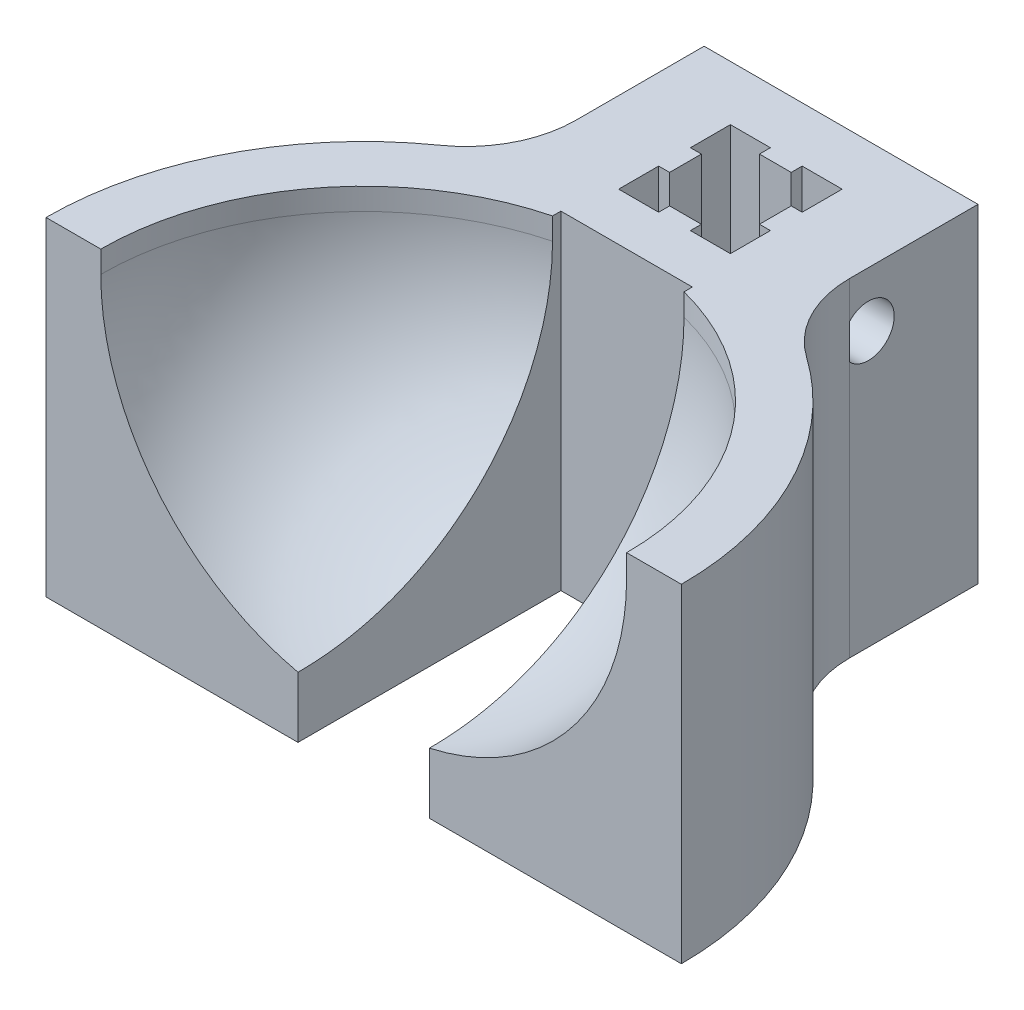
SolidWorks part; units mm, degrees
ref_plane "Front Plane" through (0, 0, 0) normal (0, 0, 1) x (1, 0, 0)
ref_plane "Top Plane" through (0, 0, 0) normal (0, 1, 0) x (1, 0, 0)
ref_plane "Right Plane" through (0, 0, 0) normal (1, 0, 0) x (0, 0, -1)
ref_axis "Axe1" through (0, -1.5691, 0) along (0, 1, 0)
sketch "Esquisse2" plane through (0, 0, 0) normal (-1, 0, 0) x (0, 0, 1)
  line L0 (-24, 30) -> (-29, 30)
  line L1 (-29, 30) -> (-29, 0)
  line L2 (-29, 0) -> (0, 0)
  line L3 (-1, 5) -> (0, 5)
  line L4 (-24, 30) -> (-24, 28)
  line L6 (0, 5) -> (0, 0)
  line L7 (0, -1.5691) -> (0, 32.9511) construction
  arc A0 (-24, 28) -> (-1, 5) centre (-1, 28) ccw
  dimension "D3" = 23
  dimension "D1" = 5
  dimension "D2" = 1
  dimension "D4" = 30
  dimension "D5" = 5
revolve "Révolution1" add sketch "Esquisse2" angle 180 mid plane about axis through (0, -1.5691, 0) along (0, 1, 0)
sketch "Esquisse3" plane through (0, 30, 0) normal (0, -1, 0) x (1, 0, 0)
  line L1 (-6, 0) -> (6, 0)
  line L2 (-6, 0) -> (-6, -24)
  line L3 (-6, -24) -> (6, -24)
  line L4 (6, 0) -> (6, -24)
  line L8 (-6, -28.3725) -> (6, -28.3725)
  line L9 (-6, -28.3725) -> (-6, -29)
  line L10 (-6, -29) -> (6, -29)
  line L11 (6, -28.3725) -> (6, -29)
  arc A0 (-29, 0) -> (29, 0) centre (0, 0) ccw construction
  arc A1 (-24, 0) -> (24, 0) centre (0, 0) ccw construction
  point P6 (0, 0)
  dimension "D1" = 12
extrude "Ball Hole" cut sketch "Esquisse3" along normal through all
sketch "Esquisse4" plane through (0, 0, 0) normal (0, -1, 0) x (-1, 0, 0)
  line L0 (-6, 28.3725) -> (6, 28.3725) construction
  line L1 (1.45, 28.3725) -> (5.1, 28.3725)
  line L2 (1.45, 28.3725) -> (1.45, 29.3725)
  line L3 (1.45, 29.3725) -> (-1.45, 29.3725)
  line L4 (-1.45, 28.3725) -> (-1.45, 29.3725)
  line L5 (5.1, 28.3725) -> (5.1, 32.0225)
  line L6 (5.1, 32.0225) -> (4.1, 32.0225)
  line L7 (4.1, 32.0225) -> (4.1, 34.9225)
  line L8 (4.1, 34.9225) -> (5.1, 34.9225)
  line L9 (5.1, 34.9225) -> (5.1, 38.5725)
  line L10 (5.1, 38.5725) -> (1.45, 38.5725)
  line L11 (1.45, 38.5725) -> (1.45, 37.5725)
  line L12 (1.45, 37.5725) -> (-1.45, 37.5725)
  line L13 (-1.45, 37.5725) -> (-1.45, 38.5725)
  line L14 (-1.45, 38.5725) -> (-5.1, 38.5725)
  line L15 (-5.1, 38.5725) -> (-5.1, 34.9225)
  line L16 (-5.1, 34.9225) -> (-4.1, 34.9225)
  line L17 (-4.1, 34.9225) -> (-4.1, 32.0225)
  line L18 (-4.1, 32.0225) -> (-5.1, 32.0225)
  line L19 (-5.1, 32.0225) -> (-5.1, 28.3725)
  line L20 (-5.1, 28.3725) -> (-1.45, 28.3725)
  line L21 (5.1, 32.0225) -> (12.5, 32.0225) construction
  line L22 (12.5, 24) -> (-12.5, 24)
  line L23 (12.5, 24) -> (12.5, 43.5725)
  line L24 (12.5, 43.5725) -> (-12.5, 43.5725)
  line L25 (-12.5, 24) -> (-12.5, 43.5725)
  line L26 (-5.1, 32.0225) -> (-12.5, 32.0225) construction
  line L27 (6, 24) -> (-6, 24) construction
  point P7 (0, 28.3725)
  point P40 (0, 29.3725)
  dimension "D1" = 2.9
  dimension "D2" = 1
  dimension "D3" = 10.2
  dimension "D4" = 10.2
  dimension "D5" = 5
  dimension "D6" = 25
extrude "Fixing Support" add sketch "Esquisse4" against normal through all
fillet "Congé1" radius 10 2 edges at (-12.5, 15, -26.1677) (12.5, 15, -26.1677)
sketch "Esquisse5" plane through (0, 0, -43.5725) normal (0, 0, -1) x (-1, 0, 0)
  line L0 (-12.5, 30) -> (-12.5, 0) construction
  line L3 (0, -1.5691) -> (0, 32.9511) construction
  line L4 (6, 0) -> (-6, 0) construction
  line L5 (6, 30) -> (-6, 30) construction
  circle A0 centre (0, 10) radius 1.6
  circle A1 centre (0, 20) radius 1.6
  point P6 (-12.5, 15)
  point P7 (0, 23.8506)
  dimension "D1" = 3.2
  dimension "D2" = 10
  dimension "D3" = 10
extrude "Fixing Hole" cut sketch "Esquisse5" against normal up to next
sketch "Esquisse6" plane through (-12.5, 0, 0) normal (-1, 0, 0) x (0, 0, 1)
  line L2 (-43.5725, 30) -> (-43.5725, 0) construction
  line L3 (-31.8551, 30) -> (-43.5725, 30) construction
  circle A0 centre (-33.5725, 25) radius 2.35
  dimension "D1" = 4.7
  dimension "D2" = 10
  dimension "D3" = 5
extrude "Ressort Hole" cut sketch "Esquisse6" against normal blind 7
mirror "Symétrie1" about plane through (0, 0, 0) normal (1, 0, 0) of "Ressort Hole"
